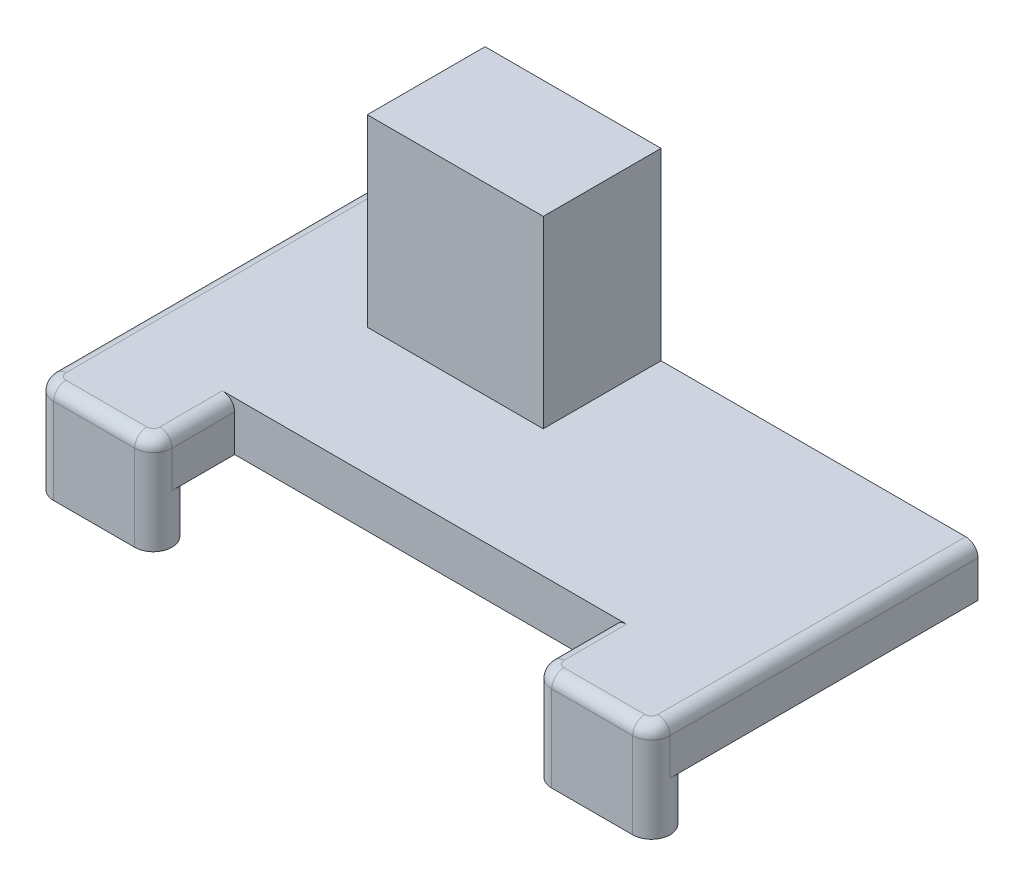
SolidWorks part; units mm, degrees
ref_plane "Front" through (0, 0, 0) normal (0, 0, 1) x (1, 0, 0)
ref_plane "Top" through (0, 0, 0) normal (0, 1, 0) x (1, 0, 0)
ref_plane "Right" through (0, 0, 0) normal (1, 0, 0) x (0, 0, -1)
sketch "Sketch1" plane through (0, 0, 0) normal (0, 1, 0) x (1, 0, 0)
  line L0 (0, -55) -> (0, 55) construction
  line L5 (-23.6, 10.5423) -> (-17, 10.5423)
  line L6 (-23.6, 7.4923) -> (-17, 7.4923)
  line L7 (23.6, 7.4923) -> (17, 7.4923)
  line L8 (23.6, 10.5423) -> (17, 10.5423)
  arc A0 (-23.6, 10.5423) -> (-23.6, 7.4923) centre (-23.6, 9.0173) ccw
  arc A1 (-17, 7.4923) -> (-17, 10.5423) centre (-17, 9.0173) ccw
  arc A2 (23.6, 10.5423) -> (23.6, 7.4923) centre (23.6, 9.0173) cw
  arc A3 (17, 7.4923) -> (17, 10.5423) centre (17, 9.0173) cw
  dimension "D1" = 3.05
  dimension "D2" = 6.6
  dimension "D3" = 17
extrude "Boss-Extrude1" add sketch "Sketch1" along normal blind 4
sketch "Sketch3" plane through (0, 4, 0) normal (0, 1, 0) x (1, 0, 0)
  line L1 (17, 7.4923) -> (23.6, 7.4923) construction
  line L2 (-23.6, 7.4923) -> (-17, 7.4923) construction
  line L5 (17, 7.4923) -> (23.6, 7.4923)
  line L6 (-23.6, 7.4923) -> (-17, 7.4923)
  line L8 (-25.125, 9.0173) -> (-25.125, 17.3059)
  line L9 (-15.475, 14.1173) -> (15.475, 14.1173)
  line L11 (-25.125, 34.1173) -> (25.125, 34.1173)
  line L13 (-15.475, 9.0173) -> (-15.475, 14.1173)
  line L14 (0, -55) -> (0, 55) construction
  line L15 (23.6, 7.4923) -> (17, 7.4923)
  line L16 (15.475, 9.0173) -> (15.475, 14.1173)
  line L17 (15.475, 14.1173) -> (-15.475, 14.1173)
  line L18 (-25.125, 17.3059) -> (-25.125, 34.1173)
  line L19 (25.125, 34.1173) -> (25.125, 17.3059)
  line L20 (25.125, 9.0173) -> (25.125, 17.3059)
  arc A0 (23.6, 7.4923) -> (23.6, 10.5423) centre (23.6, 9.0173) ccw construction
  arc A1 (17, 10.5423) -> (17, 7.4923) centre (17, 9.0173) ccw construction
  arc A2 (-23.6, 10.5423) -> (-23.6, 7.4923) centre (-23.6, 9.0173) ccw construction
  arc A3 (-17, 7.4923) -> (-17, 10.5423) centre (-17, 9.0173) ccw construction
  arc A4 (23.6, 7.4923) -> (25.125, 9.0173) centre (23.6, 9.0173) ccw
  arc A5 (15.475, 9.0173) -> (17, 7.4923) centre (17, 9.0173) ccw
  arc A6 (-25.125, 9.0173) -> (-23.6, 7.4923) centre (-23.6, 9.0173) ccw
  arc A7 (-17, 7.4923) -> (-15.475, 9.0173) centre (-17, 9.0173) ccw
  arc A8 (25.125, 9.0173) -> (23.6, 7.4923) centre (23.6, 9.0173) cw
  arc A9 (17, 7.4923) -> (15.475, 9.0173) centre (17, 9.0173) cw
  arc M5 (-23.6, 10.5423) -> (-23.6, 7.4923) centre (-23.6, 9.0173) ccw
  line M6 (-23.6, 7.4923) -> (-17, 7.4923)
  arc M7 (-17, 7.4923) -> (-17, 10.5423) centre (-17, 9.0173) ccw
  line M8 (-17, 10.5423) -> (-23.6, 10.5423)
  dimension "D1" = 5.1
  dimension "D2" = 20
extrude "Boss-Extrude3" add sketch "Sketch3" along normal blind 4 contours L16 A5 L5 A4 L20 L19 L11 L18 L8 L13 L9 M5 M8 M7 | M8 M5 M6 M7 region at (0.5047, 4, -22.9796) region at (-20.3, 4, -9.0173)
fillet "Fillet2" radius 1 10 edges at (-25.125, 8, -21.5673) (-24.6783, 8, -7.9389) (-15.475, 8, -11.5673) (-15.9217, 8, -7.9389) (15.475, 8, -11.5673) (15.9217, 8, -7.9389) (25.125, 8, -21.5673) (24.6783, 8, -7.9389) (-20.3, 8, -7.4923) (20.3, 8, -7.4923)
sketch "Sketch4" plane through (0, 8, 0) normal (0, 1, 0) x (1, 0, 0)
  line L0 (-24.125, 34.1173) -> (24.125, 34.1173) construction
  line L1 (-15.0591, 34.1173) -> (-0.7115, 34.1173)
  line L2 (-15.0591, 34.1173) -> (-15.0591, 24.5127)
  line L3 (-15.0591, 24.5127) -> (-0.7115, 24.5127)
  line L4 (-0.7115, 34.1173) -> (-0.7115, 24.5127)
extrude "Boss-Extrude4" add sketch "Sketch4" along normal blind 15
